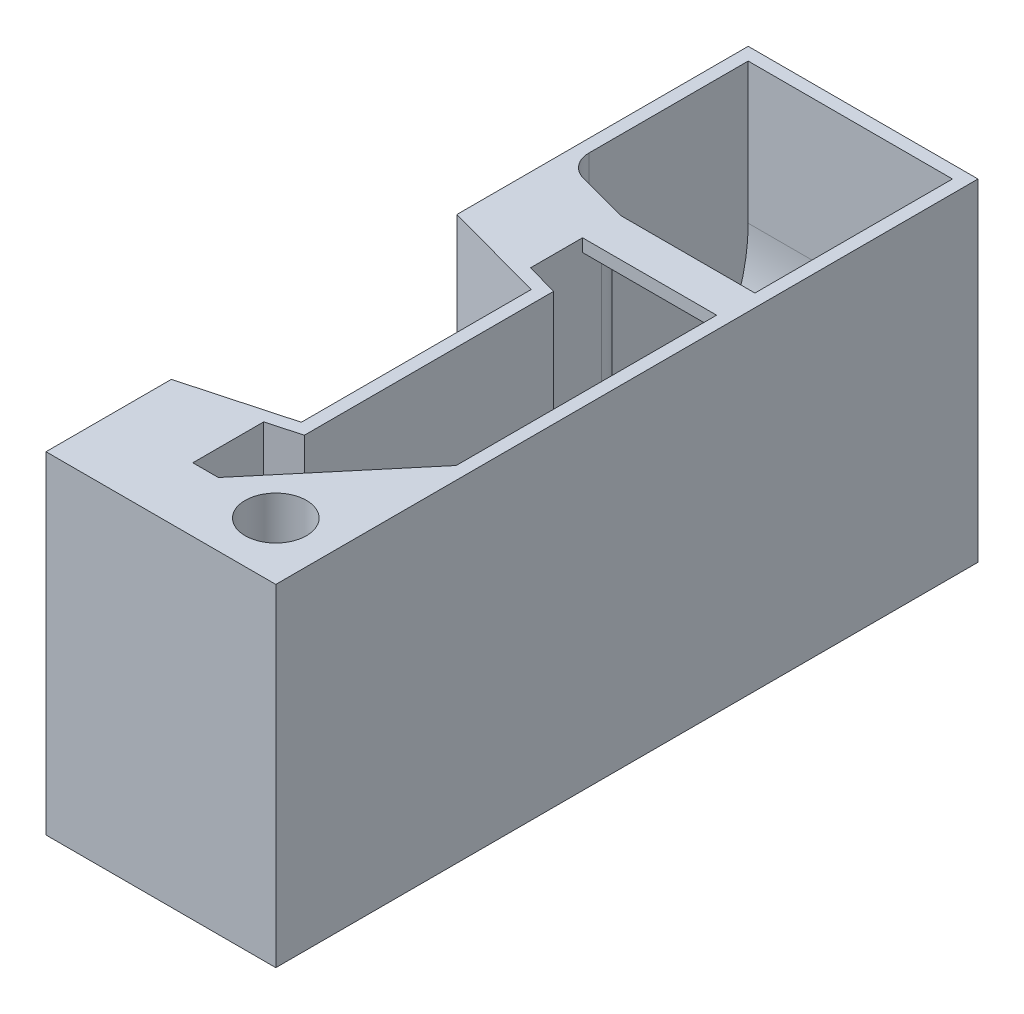
SolidWorks part; units mm, degrees
ref_plane "Front Plane" through (0, 0, 0) normal (0, 0, 1) x (1, 0, 0)
ref_plane "Top Plane" through (0, 0, 0) normal (0, 1, 0) x (1, 0, 0)
ref_plane "Right Plane" through (0, 0, 0) normal (1, 0, 0) x (0, 0, -1)
sketch "Sketch2" plane through (0, 0, 0) normal (0, -1, 0) x (1, 0, 0)
  line L0 (0, 0) -> (15, 0) construction
  line L18 (7, -12.1838) -> (7, -35)
  line L20 (7, -35) -> (25, -35)
  line L21 (25, -35) -> (25, 20)
  line L22 (25, 20) -> (7, 20)
  line L23 (7, 20) -> (7, 10.1838)
  line L24 (7, 10.1838) -> (15, 8)
  line L25 (15, 8) -> (15, -10)
  line L26 (15, -10) -> (7, -12.1838)
  point P1 (7, -12.2059)
  point P3 (7, 10.5725)
  dimension "D8" = 12.1838
  dimension "D1" = 15
  dimension "D2" = 18
  dimension "D3" = 25
  dimension "D4" = 20
  dimension "D5" = 7
  dimension "D6" = 55
  dimension "D7" = 10
  dimension "D9" = 10.1838
extrude "Boss-Extrude2" add sketch "Sketch2" along normal blind 26 separate body
shell "Shell1" thickness 1 removed face at (13.5, 0, -4.25)
fillet "Fillet1" radius 14 1 edges at (16, -25, -34)
sketch "Sketch3" plane through (0, 0, 0) normal (0, 1, 0) x (1, 0, 0)
  line L0 (13.5, 11.4461) -> (8, 12.9474)
  line L1 (8, 12.9474) -> (8, 20)
  line L2 (8, 20) -> (13.5, 18.5263)
  line L3 (13.5, 18.5263) -> (13.5, 11.4461)
  line L4 (24, 20) -> (8, 20) construction
  line L5 (13.5, -9.4461) -> (8, -10.9474)
  line L6 (13.5, -9.4461) -> (13.5, -19)
  line L7 (13.5, -19) -> (8, -19)
  line L8 (8, -10.9474) -> (8, -19)
  line L9 (10.75, -19) -> (10.75, -10.1967) construction
  line L10 (13.5, -14.223) -> (8, -14.223) construction
  line L11 (8, 12.9474) -> (8, 20) construction
  line L12 (8, -19) -> (8, -10.9474) construction
  line L13 (16, 10.7636) -> (8, 12.9474) construction
  line L14 (8, -10.9474) -> (16, -8.7636) construction
  point P3 (8, -8.7002)
  point P6 (8, -8.7002)
  point P11 (8, -10.884)
  point P12 (11, -9.7921)
  point P13 (8, -13.8501)
  point P20 (13.6738, 11.3986)
  point P23 (13.6005, -9.4186)
  point P139 (10.75, -14.223)
  dimension "D1" = 75
  dimension "D2" = 13.5
extrude "Boss-Extrude3" add sketch "Sketch3" against normal up to next
fillet "Fillet2" radius 14 1 edges at (24, -12.5, 19)
sketch "Sketch8" plane through (0, 0, 0) normal (0, 1, 0) x (1, 0, 0)
  line L0 (24, 20) -> (24, -5.4446) construction
  line L1 (24, 15.5263) -> (13.5, 15.5263)
  line L2 (24, 15.5263) -> (24, 18.5263)
  line L3 (24, 18.5263) -> (13.5, 18.5263)
  line L4 (13.5, 15.5263) -> (13.5, 18.5263)
  line L5 (18.75, 18.5263) -> (18.75, 15.5263) construction
  line L6 (24, 17.0263) -> (13.5, 17.0263) construction
  line L7 (13.5, 11.4461) -> (13.5, 18.5263) construction
  point P6 (13.5, 16.4606)
  point P9 (13.5, 18.5263)
  point P188 (18.75, 17.0263)
  dimension "D1" = 3
extrude "Boss-Extrude4" add sketch "Sketch8" against normal blind 1
fillet "Fillet4" [suppressed] radius 2
sketch "Sketch4" plane through (7, 0, 0) normal (-1, 0, 0) x (0, 0, 1)
  line L0 (13, -23) -> (-15, -23) construction
  line L1 (-1, -26) -> (-1, -23) construction
  line L4 (8, -26) -> (-10, -26) construction
  circle A0 centre (-15, -23) radius 2
  circle A1 centre (13, -23) radius 2
  dimension "D1" = 4
  dimension "D2" = 28
  dimension "D3" = 3
extrude "Cut-Extrude1" cut sketch "Sketch4" against normal blind 9
sketch "Sketch9" plane through (0, 0, 0) normal (0, 1, 0) x (1, 0, 0)
  line L0 (13.5, -15) -> (15.5, -15)
  line L1 (7, -15) -> (13.5, -15) construction
  line L2 (24, -4.8701) -> (15.5, -15)
  line L3 (24, 15.5263) -> (13.5, 15.5263)
  line L4 (24, -5.4446) -> (24, 15.5263)
  line L5 (13.5, 15.5263) -> (13.5, 11.4461)
  line L7 (24, -5.4446) -> (24, -4.8701)
  line L9 (24, 15.5263) -> (24, -5.4446) construction
  line L10 (7, -20) -> (7, -10.1838) construction
  line L11 (13.5, -19) -> (13.5, -9.4461) construction
  line L18 (13.5, -9.4461) -> (13.5, -19)
  line L19 (13.5, -15) -> (13.5, -19)
  line L20 (16, -8.7636) -> (13.5, -9.4461)
  line L22 (16, 10.7636) -> (16, -8.7636)
  line L24 (13.5, 11.4461) -> (16, 10.7636)
  arc A2 (13.5, -19) -> (24, -5.4446) centre (10, -5.4446) ccw
  arc A4 (13.5, -19) -> (24, -5.4446) centre (10, -5.4446) ccw
  dimension "D2" = 50
  dimension "D3" = 8.5
  dimension "D1" = 0
extrude "Boss-Extrude5" add sketch "Sketch9" against normal through all
sketch "Sketch7" plane through (0, 0, 0) normal (0, 1, 0) x (1, 0, 0)
  line L0 (9.5, 17.5) -> (9.5, -15.5) construction
  line L1 (9.5, -15.5) -> (20.5, -15.5) construction
  line L2 (0, 0) -> (9.5, 0) construction
  circle A0 centre (20.5, -15.5) radius 2.4
  circle A1 centre (9.5, 17.5) radius 1.5
  point P2 (0, 0)
  dimension "D4" = 3
  dimension "D6" = 4.8
  dimension "D1" = 9.5
  dimension "D2" = 17.5
  dimension "D3" = 11
  dimension "D5" = 15.5
extrude "Cut-Extrude2" cut sketch "Sketch7" against normal blind 4.7625 contours A0 region at (20.5, 0, 15.5)
fillet "Fillet5" radius 2 2 edges at (13.5, -13, -18.5263) (8, -12.5, -20)
